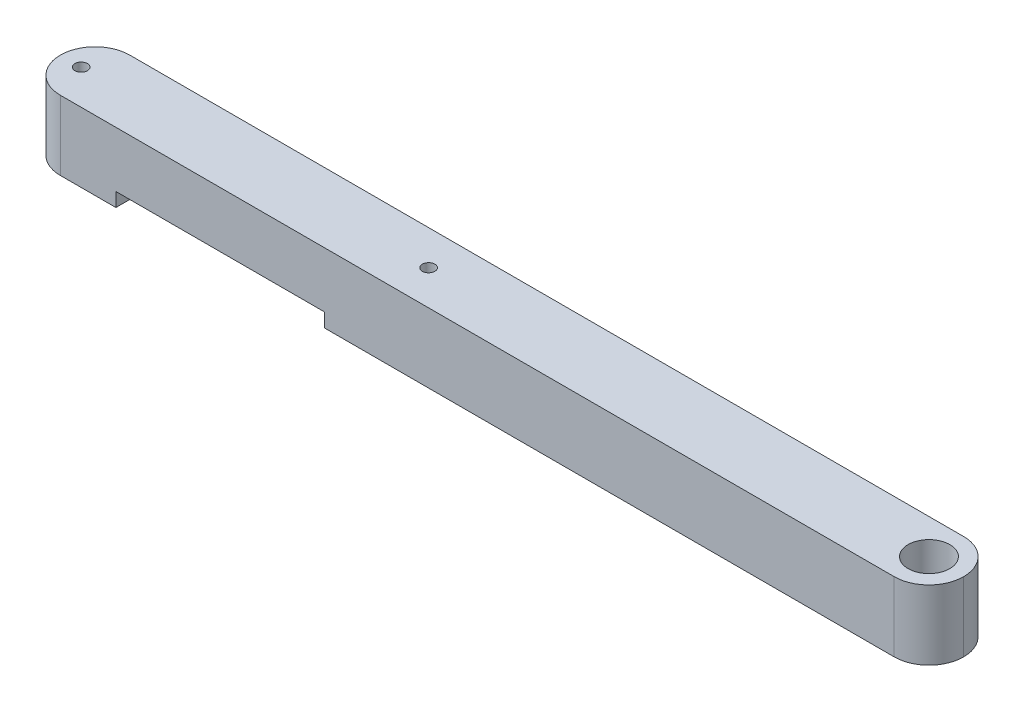
SolidWorks part; units mm, degrees
ref_plane "Front Plane" through (0, 0, 0) normal (0, 0, 1) x (1, 0, 0)
ref_plane "Top Plane" through (0, 0, 0) normal (0, 1, 0) x (1, 0, 0)
ref_plane "Right Plane" through (0, 0, 0) normal (1, 0, 0) x (0, 0, -1)
sketch "Sketch1" plane through (0, 0, 0) normal (0, 1, 0) x (1, 0, 0)
  line L1 (0, 0) -> (130, 0)
  line L2 (0, 0) -> (0, 10)
  line L3 (0, 10) -> (130, 10)
  line L4 (130, 0) -> (130, 10)
  circle A0 centre (3, 5) radius 0.9
  circle A1 centre (53, 5) radius 0.9
  circle A2 centre (125, 5) radius 3
  dimension "D3" = 3
  dimension "D4" = 50
  dimension "D1" = 130
  dimension "D2" = 10
extrude "Boss-Extrude1" add sketch "Sketch1" along normal blind 10
sketch "Sketch2" plane through (0, 0, 0) normal (0, 0, 1) x (1, 0, 0)
  line L0 (0, 0) -> (130, 0) construction
  line L1 (13, 0) -> (43, 0)
  line L2 (13, 0) -> (13, 2)
  line L3 (13, 2) -> (43, 2)
  line L4 (43, 0) -> (43, 2)
extrude "Cut-Extrude1" cut sketch "Sketch2" against normal through all both and the other way through all
fillet "Fillet1" radius 5 4 edges at (130, 5, 0) (130, 5, -10) (0, 5, 0) (0, 5, -10)
